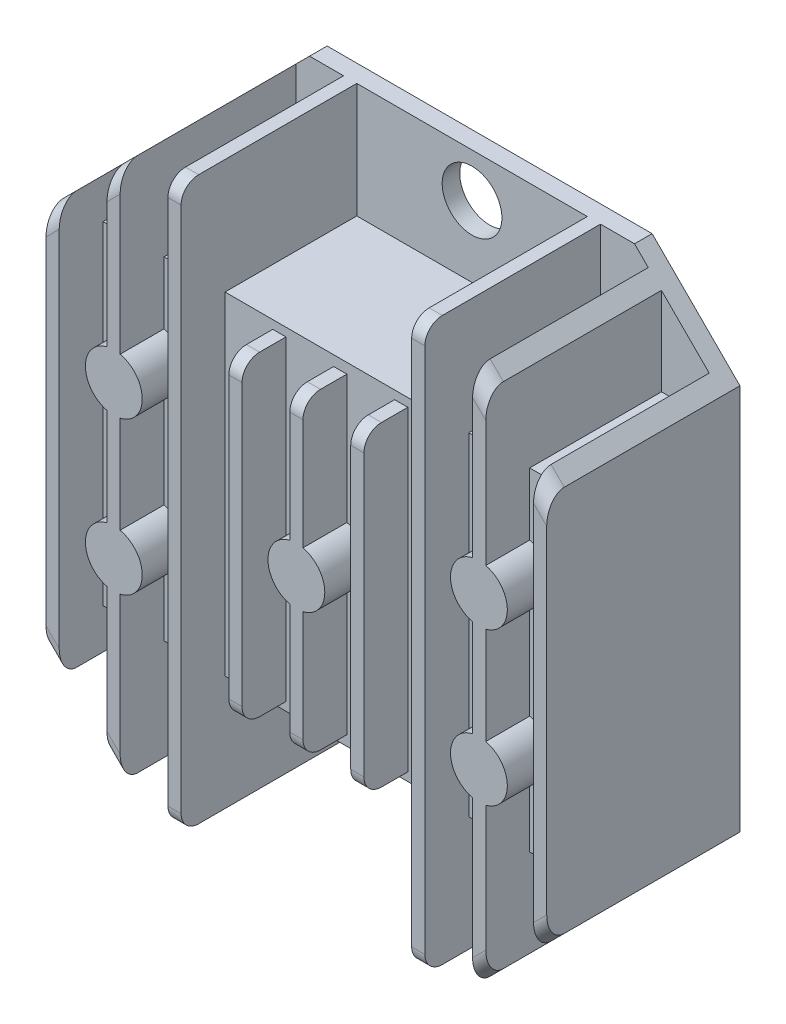
SolidWorks part; units mm, degrees
ref_plane "Ebene vorne" through (0, 0, 0) normal (1, 0, 0) x (0, 1, 0)
ref_plane "Ebene oben" through (0, 0, 0) normal (0, 0, 1) x (0, 1, 0)
ref_plane "Ebene rechts" through (0, 0, 0) normal (0, 1, 0) x (-1, 0, 0)
sketch "Skizze1" plane through (0, 0, 0) normal (0, 0, 1) x (0, 1, 0)
  line L0 (0, 48.454) -> (0, -48.454) construction
  line L5 (22, 28.5) -> (32, 18.5)
  line L7 (0, -28.5) -> (22, -28.5)
  line L8 (0, -28.5) -> (0, 28.5)
  line L9 (0, 28.5) -> (22, 28.5)
  line L10 (32, -18.5) -> (32, 18.5)
  line L11 (22, -28.5) -> (32, -18.5)
  line L12 (32, 0) -> (27, 0) construction
  circle A0 centre (27, 0) radius 3.4
  point P3 (0, 0)
  point P5 (32, 28.5)
  point P9 (32, -28.5)
  dimension "D4" = 6.8
  dimension "D1" = 64
  dimension "D2" = 57
  dimension "D3" = 5
extrude "Aufsatz-Linear austragen1" add sketch "Skizze1" along normal blind 2
sketch "Skizze2" plane through (0, 0, 2) normal (0, 0, 1) x (1, 0, 0)
  line L0 (-28.5, 22) -> (-28.5, 0) construction
  line L1 (-28.5, 18.9328) -> (28.5, 18.9328)
  line L2 (-28.5, 18.9328) -> (-28.5, 0)
  line L3 (-28.5, 0) -> (28.5, 0)
  line L4 (28.5, 18.9328) -> (28.5, 0)
extrude "Aufsatz-Linear austragen2" add sketch "Skizze2" along normal blind 15
sketch "Skizze3" plane through (0, 0, 17) normal (0, 0, 1) x (1, 0, 0)
  line L1 (0, 0) -> (-34.6234, 0)
  line L2 (0, 0) -> (0, 45.1108)
  line L3 (0, 45.1108) -> (-34.6234, 45.1108)
  line L4 (-34.6234, 0) -> (-34.6234, 45.1108)
extrude "Schnitt-Linear austragen1" cut sketch "Skizze3" against normal through all both and the other way through all
sketch "Skizze4" plane through (0, 0, 17) normal (0, 0, 1) x (1, 0, 0)
  line L0 (0, 0) -> (28.5, 0) construction
  line L1 (13.125, 0) -> (14.625, 0)
  line L2 (13.125, 0) -> (13.125, 32)
  line L3 (13.125, 32) -> (14.625, 32)
  line L4 (14.625, 0) -> (14.625, 32)
  line L5 (18.5, 32) -> (0, 32) construction
  line L6 (27, 23.5) -> (28.5, 22)
  line L7 (20.0625, 0) -> (21.5625, 0)
  line L8 (20.0625, 0) -> (20.0625, 30.4375)
  line L10 (21.5625, 0) -> (21.5625, 28.9375)
  line L11 (28.5, 0) -> (27, 0)
  line L12 (28.5, 0) -> (28.5, 22)
  line L14 (27, 0) -> (27, 23.5)
  line L16 (28.5, 22) -> (18.5, 32) construction
  line L17 (0, 0) -> (0, 18.9328) construction
  line L18 (6.1875, 17.9729) -> (7.6875, 17.9729)
  line L19 (6.1875, 17.9729) -> (6.1875, 0)
  line L20 (6.1875, 0) -> (7.6875, 0)
  line L21 (7.6875, 17.9729) -> (7.6875, 0)
  line L22 (0, 17.7756) -> (0.75, 17.7756)
  line L23 (0, 17.7756) -> (0, 0)
  line L24 (0, 0) -> (0.75, 0)
  line L25 (0.75, 17.7756) -> (0.75, 0)
  line L26 (0.75, 5.8395) -> (6.1875, 5.8395) construction
  line L27 (7.6875, 5.8395) -> (13.125, 5.8395) construction
  line L28 (14.625, 5.8395) -> (20.0625, 5.8395) construction
  line L29 (21.5625, 5.8395) -> (27, 5.8395) construction
  line L30 (20.0625, 30.4375) -> (21.5625, 28.9375)
  dimension "D1" = 1.5
  dimension "D2" = 0.75
extrude "Aufsatz-Linear austragen3" add sketch "Skizze4" against normal up to surface (15 mm away) and the other way blind 5 up to face at (11.2714, 25.4094, 2)
fillet "Verrundung1" radius 2 5 edges at (0.375, 17.7756, 22) (6.9375, 17.9729, 22) (27.75, 22.75, 22) (20.8125, 29.6875, 22) (13.875, 32, 22)
sketch "Skizze5" plane through (0, 0, 22) normal (0, 0, 1) x (1, 0, 0)
  circle A0 centre (20.7826, 8.6781) radius 3.2346
extrude "Aufsatz-Linear austragen4" add sketch "Skizze5" against normal up to surface (5 mm away) up to face at (24.2812, 9.4664, 17)
sketch "Skizze6" plane through (0, 0, 17) normal (0, 0, 1) x (1, 0, 0)
  line L0 (3.2346, 0) -> (0, 0)
  line L2 (0, 0) -> (0, 3.2346)
  arc A0 (3.2346, 0) -> (0, 3.2346) centre (0, 0) ccw
  arc A2 (20.0625, 11.8315) -> (20.0625, 5.5247) centre (20.7826, 8.6781) ccw construction
  line M2 (0.75, 0) -> (6.1875, 0)
  line M11 (0.75, 17.7756) -> (0.75, 0)
extrude "Aufsatz-Linear austragen7" add sketch "Skizze6" along normal up to surface (5 mm away) contours A0 M2 M11 | A0 L2 L0 M11 region at (1.7861, 1.2777, 17) region at (0.3733, 1.6028, 17) up to face at (0.375, 7.8878, 22)
mirror "Spiegeln1" about plane through (28.5, 0, 2) normal (0, 1, 0) of bodies 106
mirror "Spiegeln2" about plane through (0, 0, 0) normal (1, 0, 0) of bodies 107
sketch "Skizze7" plane through (-28.5, 0, 0) normal (-1, 0, 0) x (0, -1, 0)
  circle A0 centre (-3, 2.8859) radius 1.5
  circle A1 centre (0, 2.8859) radius 1.5
  circle A2 centre (3, 2.8859) radius 1.5
  dimension "D1" = 3
extrude "Aufsatz-Linear austragen9" add sketch "Skizze7" along normal blind 11 separate body contours A0 | A1 | A2 region at (-28.5, 3, 2.8859) region at (-28.5, -3, 2.8859) region at (-28.5, 0, 2.8859)
